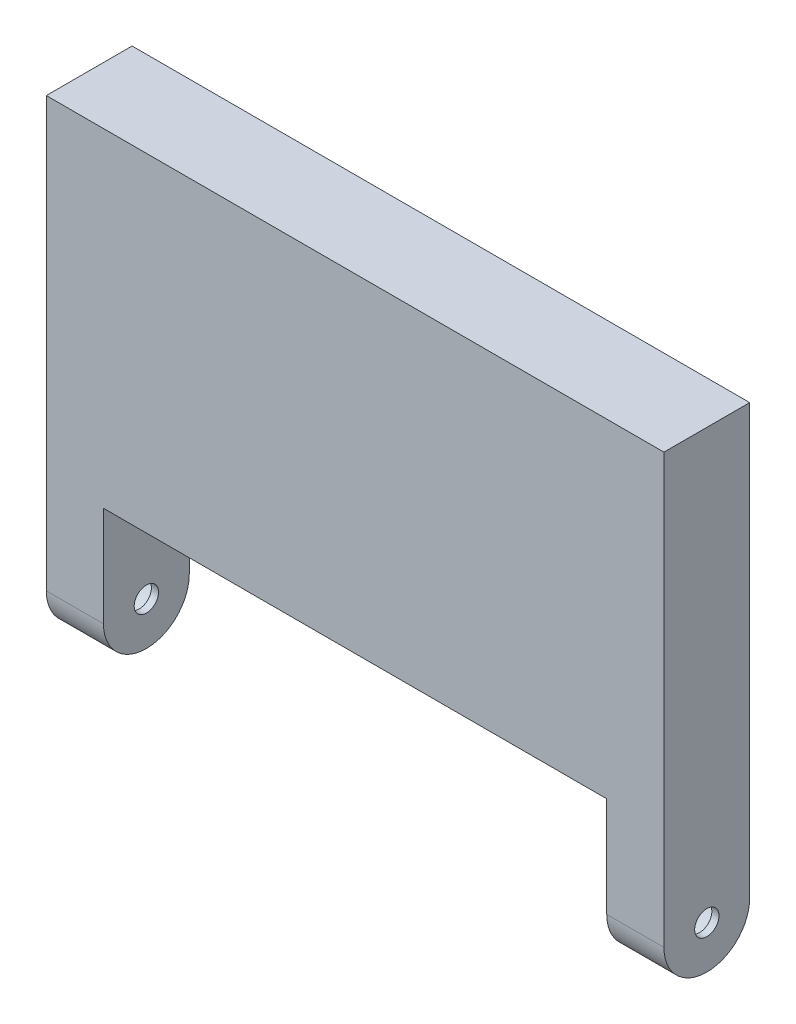
SolidWorks part; units mm, degrees
ref_plane "Front Plane" through (0, 0, 0) normal (0, 0, 1) x (1, 0, 0)
ref_plane "Top Plane" through (0, 0, 0) normal (0, 1, 0) x (1, 0, 0)
ref_plane "Right Plane" through (0, 0, 0) normal (1, 0, 0) x (0, 0, -1)
sketch "Sketch1" plane through (0, 0, 0) normal (0, 0, 1) x (1, 0, 0)
  line L0 (-276.0597, 0) -> (276.0597, 0) construction
  line L1 (-216, -30) -> (-216, 300)
  line L2 (-216, 300) -> (0, 300)
  line L3 (-216, -30) -> (-176, -30)
  line L4 (0, -283.5322) -> (0, 283.5322) construction
  line L5 (-176, -30) -> (-176, 70)
  line L6 (-176, 70) -> (0, 70)
  line L7 (-238.394, -30) -> (238.394, -30) construction
  line L8 (-181, 75) -> (0, 75)
  line L9 (-181, -25) -> (-181, 75)
  line L10 (-211, -25) -> (-181, -25)
  line L11 (-211, -25) -> (-211, 295)
  line L12 (-211, 295) -> (0, 295)
  point P10 (0, -30)
  dimension "D1" = 432
  dimension "D2" = 100
  dimension "D3" = 60
  dimension "D4" = 300
  dimension "D5" = 352
  dimension "D6" = 5
sketch "Sketch3" plane through (0, 0, 0) normal (1, 0, 0) x (0, 0, -1)
  line L0 (0, 0) -> (0, -30) construction
  line L1 (0, -283.5322) -> (0, 283.5322) construction
  line L2 (-30, 0) -> (-30, 300)
  line L3 (-30, 300) -> (30, 300)
  line L4 (30, 300) -> (30, 0)
  line L5 (30, 70) -> (-30, 70)
  line L6 (25, 295) -> (25, 0)
  line L7 (-25, 0) -> (-25, 295)
  line L8 (-25, 295) -> (25, 295)
  line L9 (30, 75) -> (-30, 75)
  arc A0 (-30, 0) -> (30, 0) centre (0, 0) ccw
  arc A1 (-25, 0) -> (25, 0) centre (0, 0) ccw
  dimension "D2" = 5
  dimension "D1" = 5
extrude "Boss-Extrude1" add sketch "Sketch3" along normal up to vertex (-211 mm away) from vertex contours L9 L6 L8 L7 | L9 L4 L3 L2 L7 L8 L6 | L6 L9 L7 L5 | L4 L9 L6 L5 | L7 L9 L2 L5 | L0 A1 L7 L5 L2 A0 | A1 L0 A0 L4 L5 L6 | L7 A1 L6 L5 region at (0, -18.4159, -18.4159) region at (0, -27.5, 1.044) region at (0, 25.0088, 0) region at (0, 72.5, 0) region at (0, 72.5, 27.5) region at (0, 72.5, -27.5) region at (0, 77.3286, 27.5) region at (0, 185, 0) up to point (-211, -25, 0) starting at point (-216, -30, 0)
extrude "Boss-Extrude2" add sketch "Sketch3<4>" along normal up to vertex (-181 mm away) from vertex contours L9 L4 L3 L2 L7 L8 L6 | L7 L9 L2 L5 | L0 A1 L7 L5 L2 A0 | L4 L9 L6 L5 | A1 L0 A0 L4 L5 L6 region at (0, -18.4159, -18.4159) region at (0, -27.5, 1.044) region at (0, 72.5, 27.5) region at (0, 72.5, -27.5) region at (0, 77.3286, 27.5) up to point (-181, -25, 0) starting at point (-211, -25, 0)
sketch "Sketch3<4>" plane through (0, 0, 0) normal (1, 0, 0) x (0, 0, -1) same geometry as "Sketch3"
extrude "Boss-Extrude3" add sketch "Sketch3<5>" along normal up to vertex (-176 mm away) from vertex contours L9 L4 L3 L2 L7 L8 L6 | L7 L9 L2 L5 | L4 L9 L6 L5 | L6 L9 L7 L5 | A1 L0 A0 L4 L5 L6 | L7 A1 L6 L5 | L0 A1 L7 L5 L2 A0 region at (0, -18.4159, -18.4159) region at (0, -27.5, 1.044) region at (0, 25.0088, 0) region at (0, 72.5, 0) region at (0, 72.5, 27.5) region at (0, 72.5, -27.5) region at (0, 77.3286, 27.5) up to point (-176, -30, 0) starting at point (-181, -25, 0)
sketch "Sketch3<5>" plane through (0, 0, 0) normal (1, 0, 0) x (0, 0, -1) same geometry as "Sketch3"
extrude "Boss-Extrude4" add sketch "Sketch3<6>" along normal up to surface from vertex contours L9 L4 L3 L2 L7 L8 L6 | L7 L9 L2 L5 | L6 L9 L7 L5 | L4 L9 L6 L5 region at (0, 72.5, 27.5) region at (0, 187.5, 27.6714) region at (0, 72.5, 0) region at (0, 72.5, -27.5) up to plane "Right Plane" starting at point (-176, 70, 0)
sketch "Sketch3<6>" plane through (0, 0, 0) normal (1, 0, 0) x (0, 0, -1) same geometry as "Sketch3"
sketch "Sketch6" plane through (0, 0, 0) normal (1, 0, 0) x (0, 0, -1)
  line L0 (0, -283.5322) -> (0, 283.5322) construction
  circle A0 centre (0, 0) radius 8.5
  dimension "D1" = 17
extrude "Cut-Extrude1" cut sketch "Sketch6" against normal through all
mirror "Mirror5" about plane through (0, 0, 0) normal (1, 0, 0) of bodies 108 104
equation "\"D2@Sketch3\"=\"D1@Sketch3\""
